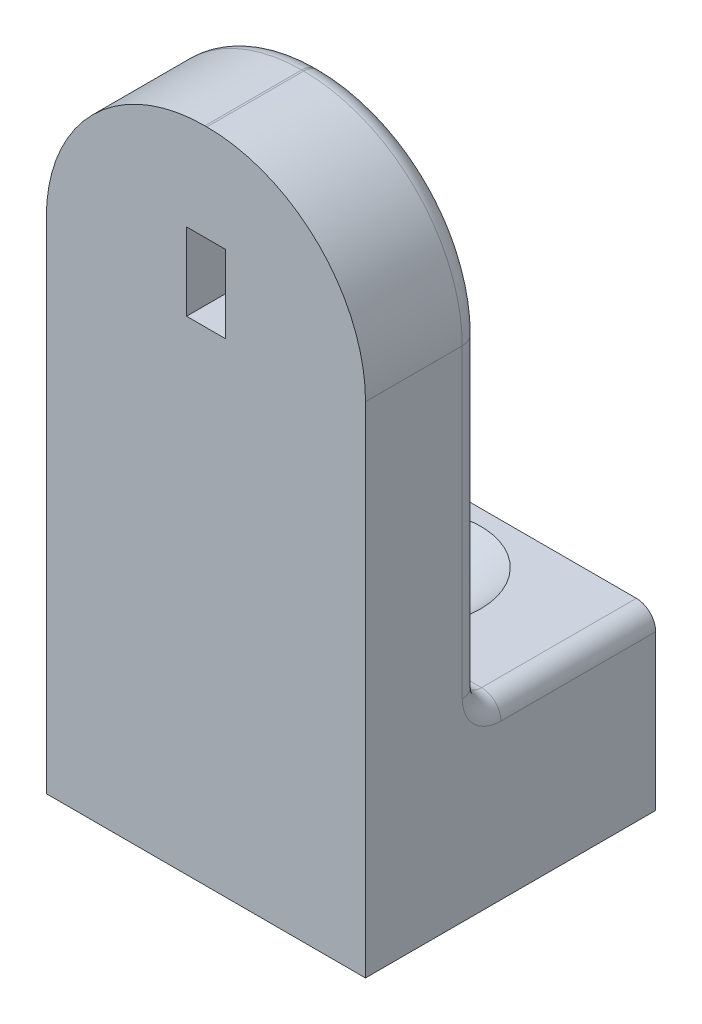
SolidWorks part; units mm, degrees
ref_plane "Front Plane" through (0, 0, 0) normal (0, 0, 1) x (1, 0, 0)
ref_plane "Top Plane" through (0, 0, 0) normal (0, 1, 0) x (1, 0, 0)
ref_plane "Right Plane" through (0, 0, 0) normal (1, 0, 0) x (0, 0, -1)
sketch "Sketch1" plane through (0, 0, 0) normal (0, 1, 0) x (1, 0, 0)
  line L1 (-8.25, 7.5) -> (8.25, 7.5)
  line L2 (-8.25, 7.5) -> (-8.25, -7.5)
  line L3 (-8.25, -7.5) -> (8.25, -7.5)
  line L4 (8.25, 7.5) -> (8.25, -7.5)
  line L5 (-8.25, 7.5) -> (8.25, -7.5) construction
  line L6 (-8.25, -7.5) -> (8.25, 7.5) construction
  circle A0 centre (0, 3) radius 2.2
  point P0 (0, 0)
  dimension "D3" = 4.4
  dimension "D1" = 16.5
  dimension "D2" = 15
  dimension "D4" = 4.5
extrude "Boss-Extrude1" add sketch "Sketch1" along normal blind 9
chamfer "Chamfer1" distance 1.5 angle 45 1 edges at (0, 9, -0.8)
sketch "Sketch2" plane through (0, 9, 0) normal (0, 1, 0) x (1, 0, 0)
  line L0 (-8.25, 7.5) -> (-8.25, -7.5) construction
  line L1 (-8.25, -1.5) -> (8.25, -1.5)
  line L2 (-8.25, -1.5) -> (-8.25, -7.5)
  line L3 (-8.25, -7.5) -> (8.25, -7.5)
  line L4 (8.25, -1.5) -> (8.25, -7.5)
  line L5 (8.25, -7.5) -> (8.25, 7.5) construction
  dimension "D1" = 6
extrude "Boss-Extrude2" add sketch "Sketch2" along normal blind 25
sketch "Sketch4" plane through (0, 0, 1.5) normal (0, 0, -1) x (-1, 0, 0)
  line L0 (0, 25) -> (0, 29) construction
  line L1 (-1, 29) -> (1, 29)
  line L2 (-1, 29) -> (-1, 25)
  line L3 (-1, 25) -> (1, 25)
  line L4 (1, 29) -> (1, 25)
  line L5 (-8.25, 34) -> (8.25, 34) construction
  line L6 (-2, 30) -> (2, 30)
  line L7 (2, 30) -> (2, 24)
  line L8 (-2, 24) -> (2, 24)
  line L9 (-2, 30) -> (-2, 24)
  dimension "D1" = 2
  dimension "D2" = 4
  dimension "D3" = 5
  dimension "D4" = 1
extrude "Cut-Extrude2" cut sketch "Sketch4" against normal through all both contours L0 L3 L4 L1 | L3 L0 L1 L2 region at (0.5, 27, 1.5) region at (-0.5, 27, 1.5)
extrude "Cut-Extrude3" cut sketch "Sketch4<3>" against normal blind 1 contours L6 L9 L8 L7 L1 L4 L3 L2 region at (0, 29.9279, 1.5)
sketch "Sketch4<3>" plane through (0, 0, 1.5) normal (0, 0, -1) x (-1, 0, 0) same geometry as "Sketch4"
fillet "Fillet1" radius 1 6 edges at (8.25, 21.5, 1.5) (-8.25, 9, -3) (0, 34, 1.5) (8.25, 9, -3) (-8.25, 21.5, 1.5) (0, 9, 1.5)
sketch "Sketch7" plane through (0, 0, 2.5) normal (0, 0, -1) x (-1, 0, 0)
  line L0 (-2, 30) -> (-2, 24) construction
  line L1 (-2, 25) -> (2, 25)
  line L2 (-2, 25) -> (-2, 24)
  line L3 (-2, 24) -> (2, 24)
  line L4 (2, 25) -> (2, 24)
  line L5 (-1, 25) -> (1, 25) construction
extrude "Boss-Extrude4" add sketch "Sketch7" along normal blind 1
fillet "Fillet2" radius 8.2 4 edges at (7.9571, 33.7071, 1.7929) (-7.9571, 33.7071, 1.7929) (-8.25, 34, 5) (8.25, 34, 5)
